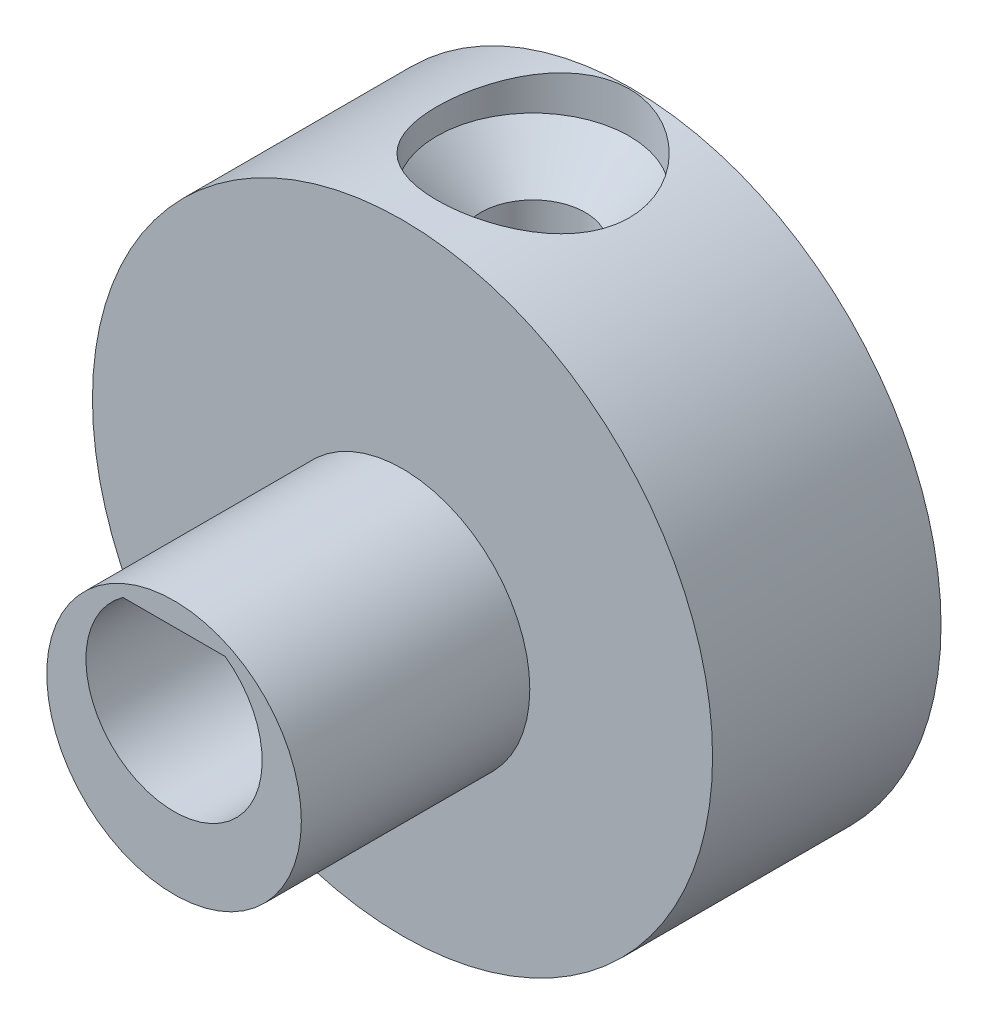
SolidWorks part; units mm, degrees
ref_plane "Plan de face" through (0, 0, 0) normal (0, 0, 1) x (1, 0, 0)
ref_plane "Plan de dessus" through (0, 0, 0) normal (0, 1, 0) x (1, 0, 0)
ref_plane "Plan de droite" through (0, 0, 0) normal (1, 0, 0) x (0, 0, -1)
sketch "Esquisse1" plane through (0, 0, 0) normal (0, 0, 1) x (1, 0, 0)
  line L0 (-1.5, 2) -> (1.5, 2) construction
  line L1 (-1.5652, 2.2) -> (1.5652, 2.2)
  arc A0 (-1.5, 2) -> (1.5, 2) centre (0, 0) ccw construction
  circle A2 centre (0, 0) radius 9.5
  arc A3 (-1.5652, 2.2) -> (1.5652, 2.2) centre (0, 0) ccw
  dimension "D1" = 2.5
  dimension "D2" = 2
  dimension "D3" = 0.2
  dimension "D4" = 19
extrude "Boss.-Extru.1" add sketch "Esquisse1" along normal blind 7 contours A0 L0 | A2 region at (-9.2313, 0, 0)
sketch "Esquisse2" plane through (0, 0, 0) normal (0, 0, -1) x (-1, 0, 0)
  line L0 (1.5652, 2.2) -> (-1.5652, 2.2) construction
  line L1 (-2.9, 3.2) -> (2.9, 3.2)
  line L2 (-2.9, 3.2) -> (-2.9, 5.6)
  line L3 (-2.9, 5.6) -> (2.9, 5.6)
  line L4 (2.9, 3.2) -> (2.9, 5.6)
  line L5 (-2.9, 3.2) -> (2.9, 5.6) construction
  line L6 (-2.9, 5.6) -> (2.9, 3.2) construction
  point P0 (0, 4.4)
  point P14 (0, 0)
  point P15 (0, 0)
  dimension "D1" = 2.4
  dimension "D2" = 5.8
  dimension "D3" = 1
extrude "Enlèv. mat.-Extru.1" cut sketch "Esquisse2" against normal blind 6
sketch "Esquisse3" plane through (0, 3.2, 0) normal (0, 1, 0) x (1, 0, 0)
  circle A0 centre (0, -3) radius 1.6
  dimension "D1" = 3.2
  dimension "D2" = 3
extrude "Enlèv. mat.-Extru.2" cut sketch "Esquisse3" against normal up to next and the other way up to next
ref_plane "Plan2" through (0, 8.9, 0) normal (0, 1, 0) x (1, 0, 0)
sketch "Esquisse7" plane through (0, 8.9, 0) normal (0, 1, 0) x (1, 0, 0)
  circle A0 centre (0, -3) radius 2.95
  dimension "D1" = 5.9
extrude "Enlèv. mat.-Extru.8" cut sketch "Esquisse7" along normal through all
chamfer "Chanfrein1" distance 2 angle 45 1 edges at (0, 8.9, 4.6)
sketch "Esquisse9" plane through (0, 0, 7) normal (0, 0, 1) x (1, 0, 0)
  line L0 (-1.5, 2) -> (1.5, 2) construction
  line L1 (-1.5652, 2.2) -> (1.5652, 2.2)
  circle A1 centre (0, -1) radius 3.9
  arc A2 (-1.5, 2) -> (1.5, 2) centre (0, 0) ccw construction
  arc A3 (-1.5652, 2.2) -> (1.5652, 2.2) centre (0, 0) ccw
  dimension "D1" = 7.8
  dimension "D3" = 5
  dimension "D2" = 1
  dimension "D4" = 2
  dimension "D5" = 0.2
extrude "Boss.-Extru.2" add sketch "Esquisse9" along normal blind 7
